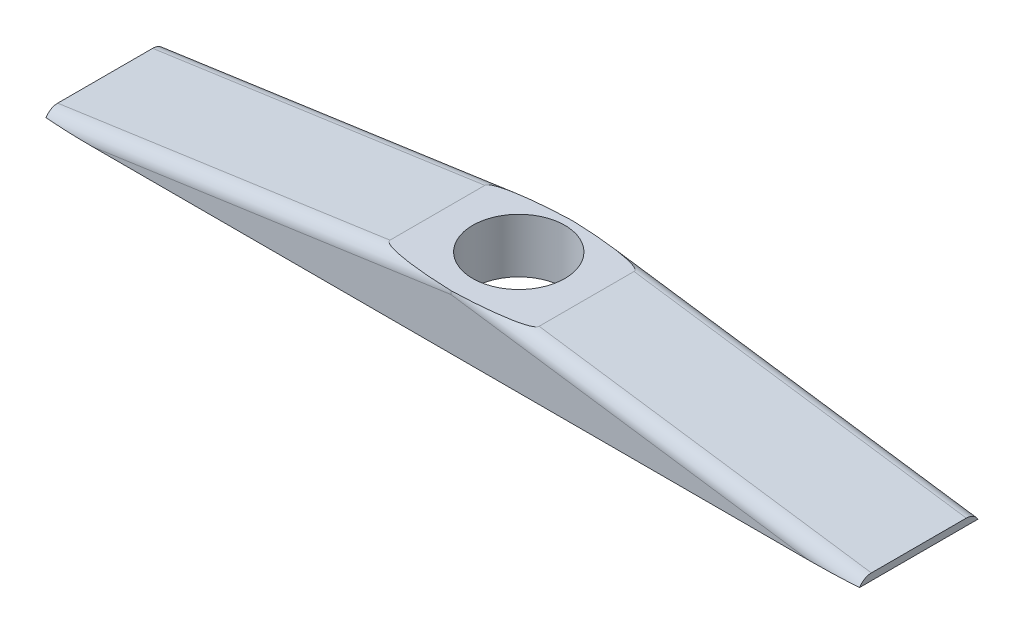
SolidWorks part; units mm, degrees
ref_plane "Front Plane" through (0, 0, 0) normal (0, 0, 1) x (1, 0, 0)
ref_plane "Top Plane" through (0, 0, 0) normal (0, 1, 0) x (1, 0, 0)
ref_plane "Right Plane" through (0, 0, 0) normal (1, 0, 0) x (0, 0, -1)
sketch "Sketch1" plane through (0, 0, 0) normal (0, 0, 1) x (1, 0, 0)
  line L0 (0, 0) -> (0, 22.9679) construction
  line L1 (-30, 0) -> (30, 0)
  line L3 (5.5, 4) -> (-5.5, 4)
  line L5 (30, 0) -> (30, 0.5)
  line L6 (30, 0.5) -> (5.5, 4)
  line L7 (-30, 0) -> (-30, 0.5)
  line L8 (-30, 0.5) -> (-5.5, 4)
  point P7 (0, 4)
  dimension "D1" = 60
  dimension "D2" = 11
  dimension "D3" = 4
  dimension "D4" = 0.5
extrude "Boss-Extrude1" add sketch "Sketch1" along normal blind 9
sketch "Sketch2" plane through (0, 4, 0) normal (0, 1, 0) x (1, 0, 0)
  line L0 (5.5, 0) -> (-5.5, 0) construction
  circle A0 centre (0, -4) radius 3.4
  dimension "D1" = 6.8
  dimension "D2" = 4
extrude "Cut-Extrude1" cut sketch "Sketch2" against normal through all
fillet "Fillet1" radius 1 4 edges at (-17.75, 2.25, 9) (-17.75, 2.25, 0) (17.75, 2.25, 0) (17.75, 2.25, 9)
